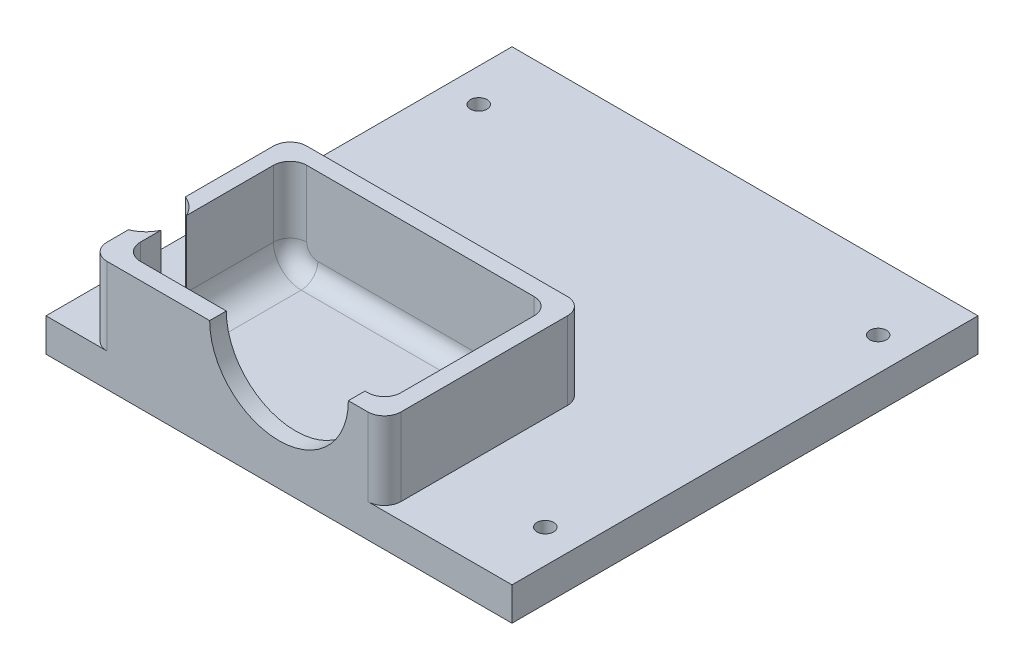
SolidWorks part; units mm, degrees
material "PVB"
ref_plane "Front Plane" through (0, 0, 0) normal (0, 0, 1) x (1, 0, 0)
ref_plane "Top Plane" through (0, 0, 0) normal (0, 1, 0) x (1, 0, 0)
ref_plane "Right Plane" through (0, 0, 0) normal (1, 0, 0) x (0, 0, -1)
sketch "Sketch1" plane through (0, 0, 0) normal (0, 1, 0) x (1, 0, 0)
  line L1 (0, 0) -> (84, 0)
  line L2 (0, 0) -> (0, 84)
  line L3 (0, 84) -> (84, 84)
  line L4 (84, 0) -> (84, 84)
  dimension "D1" = 84
  dimension "D2" = 84
extrude "Boss-Extrude1" add sketch "Sketch1" along normal blind 6
sketch "Sketch2" plane through (0, 6, 0) normal (0, 1, 0) x (1, 0, 0)
  line L0 (84, 84) -> (0, 84) construction
  line L1 (0, 84) -> (0, 0) construction
  line L2 (0, 0) -> (84, 0) construction
  line L3 (84, 0) -> (84, 84) construction
  circle A0 centre (6, 72) radius 1.5
  circle A1 centre (6, 12) radius 1.5
  circle A2 centre (78, 12) radius 1.5
  circle A3 centre (78, 72) radius 1.5
  dimension "D1" = 3
  dimension "D2" = 3
  dimension "D3" = 3
  dimension "D4" = 3
  dimension "D6" = 6
  dimension "D7" = 12
  dimension "D8" = 6
  dimension "D9" = 6
  dimension "D10" = 12
  dimension "D11" = 6
  dimension "D5" = 12
  dimension "D12" = 12
extrude "Cut-Extrude1" cut sketch "Sketch2" against normal through all
ref_plane "Plane1" through (0, 0, -42) normal (0, 0, 1) x (1, 0, 0)
sketch "Sketch4" plane through (0, 6, 0) normal (0, 1, 0) x (1, 0, 0)
  line L0 (3, 21) -> (3, 9)
  line L1 (3, 9) -> (13, 9)
  line L2 (13, 15) -> (8, 21)
  line L3 (3, 21) -> (8, 21)
  line L4 (8, 21) -> (13, 15)
  line L5 (13, 15) -> (13, 9)
  line L6 (0, 84) -> (0, 0) construction
  line L7 (0, 0) -> (84, 0) construction
  circle A0 centre (6, 12) radius 1.5
  circle A1 centre (6, 12) radius 1.5 construction
  dimension "D1" = 3
  dimension "D2" = 9
  dimension "D3" = 12
  dimension "D4" = 10
  dimension "D5" = 6
  dimension "D6" = 5
ref_plane "Plane2" through (42, 0, 0) normal (-1, 0, 0) x (0, 0, 1)
sketch "Sketch5" plane through (0, 6, 0) normal (0, 1, 0) x (1, 0, 0)
  line L0 (8, 36) -> (8, 0)
  line L1 (8, 36) -> (61, 36)
  line L2 (8, 0) -> (61, 0)
  line L3 (61, 36) -> (61, 0)
  line L4 (8, 36) -> (61, 0) construction
  line L5 (8, 0) -> (61, 36) construction
  line L6 (42, 3.3) -> (42, -3.3) construction
  line L12 (0, 0) -> (84, 0) construction
  point P1 (34.5, 18)
  dimension "D1" = 53
  dimension "D2" = 36
  dimension "D3" = 7.5
extrude "Boss-Extrude2" add sketch "Sketch5" along normal blind 22
sketch "Sketch6" plane through (0, 28, 0) normal (0, 1, 0) x (1, 0, 0)
  line L14 (58, 33) -> (11, 33)
  line L15 (11, 33) -> (11, 3)
  line L16 (11, 3) -> (58, 3)
  line L17 (58, 3) -> (58, 33)
  line L18 (58, 33) -> (11, 33)
  line L19 (11, 33) -> (11, 3)
  line L20 (11, 3) -> (58, 3)
  line L21 (58, 3) -> (58, 33)
  dimension "D1" = 3
extrude "Cut-Extrude5" cut sketch "Sketch6" against normal blind 25
fillet "Fillet1" radius 3 10 edges at (58, 15.5, -33) (11, 15.5, -33) (58, 15.5, -3) (11, 15.5, -3) (8, 17, -36) (61, 17, 0) (61, 17, -36) (8, 17, 0) (34.5, 3, -3) (34.5, 3, -33)
fillet "Fillet2" radius 5 6 edges at (11.8787, 3.8787, -3.8787) (11.8787, 3.8787, -32.1213) (57.1213, 3.8787, -32.1213) (57.1213, 3.8787, -3.8787) (58, 3, -18) (11, 3, -18)
sketch "Sketch8" plane through (0, 0, 0) normal (0, 0, 1) x (1, 0, 0)
  line L1 (0, 0) -> (84, 0) construction
  line L3 (61, 28) -> (61, 6) construction
  circle A0 centre (42, 20) radius 12.5
  dimension "D2" = 25
  dimension "D1" = 19
  dimension "D3" = 20
extrude "Cut-Extrude6" cut sketch "Sketch8" against normal blind 10
sketch "Sketch9" plane through (0, 0, 0) normal (0, 0, 1) x (1, 0, 0)
  line L0 (0, 0) -> (84, 0) construction
  line L1 (0, 28) -> (84, 28)
  line L2 (0, 28) -> (0, 20)
  line L3 (0, 20) -> (84, 20)
  line L4 (84, 28) -> (84, 20)
  line L5 (84, 6) -> (84, 0) construction
  line L6 (0, 6) -> (0, 0) construction
  line L7 (11, 28) -> (32.3953, 28) construction
  dimension "D1" = 20
extrude "Cut-Extrude7" cut sketch "Sketch9" against normal through all both and the other way through all
sketch "Sketch11" plane through (0, 0, 0) normal (0, -1, 0) x (1, 0, 0)
  line L0 (3, -9) -> (13, -9)
  line L1 (13, -9) -> (13, -15)
  line L2 (13, -15) -> (8, -21)
  line L3 (8, -21) -> (3, -21)
  line L4 (3, -21) -> (3, -9)
extrude "Cut-Extrude8" cut sketch "Sketch11" against normal blind 3
mirror "Mirror1" about plane through (0, 0, -42) normal (0, 0, 1) of "Cut-Extrude8" second plane through (42, 0, 0) second plane normal (-1, 0, 0)
sketch "Sketch13" plane through (0, 20, 0) normal (0, 1, 0) x (1, 0, 0)
  line L12 (54.5, 0) -> (58, 0)
  line L13 (61, 3) -> (61, 33)
  line L14 (58, 36) -> (11, 36)
  line L15 (8, 33) -> (8, 3)
  line L16 (11, 0) -> (29.5, 0)
  line L17 (29.5, 0) -> (29.5, 3)
  line L18 (29.5, 3) -> (14, 3)
  line L19 (11, 6) -> (11, 30)
  line L20 (14, 33) -> (55, 33)
  line L21 (58, 30) -> (58, 6)
  line L22 (55, 3) -> (54.5, 3)
  line L23 (54.5, 3) -> (54.5, 0)
  line L24 (54.5, 0) -> (58, 0)
  line L25 (61, 3) -> (61, 33)
  line L26 (58, 36) -> (11, 36)
  line L27 (8, 33) -> (8, 3)
  line L28 (11, 0) -> (29.5, 0)
  line L29 (29.5, 0) -> (29.5, 3)
  line L30 (29.5, 3) -> (14, 3)
  line L31 (11, 6) -> (11, 30)
  line L32 (14, 33) -> (55, 33)
  line L33 (58, 30) -> (58, 6)
  line L34 (55, 3) -> (54.5, 3)
  line L35 (54.5, 3) -> (54.5, 0)
  circle A0 centre (6, 12) radius 1.5 construction
  circle A1 centre (6, 12) radius 1.5
  circle A2 centre (6, 12) radius 5.5
  arc A8 (58, 0) -> (61, 3) centre (58, 3) ccw
  arc A9 (61, 33) -> (58, 36) centre (58, 33) ccw
  arc A10 (11, 36) -> (8, 33) centre (11, 33) ccw
  arc A11 (8, 3) -> (11, 0) centre (11, 3) ccw
  arc A12 (11, 6) -> (14, 3) centre (14, 6) ccw
  arc A13 (14, 33) -> (11, 30) centre (14, 30) ccw
  arc A14 (58, 30) -> (55, 33) centre (55, 30) ccw
  arc A15 (55, 3) -> (58, 6) centre (55, 6) ccw
  arc A16 (58, 0) -> (61, 3) centre (58, 3) ccw
  arc A17 (61, 33) -> (58, 36) centre (58, 33) ccw
  arc A18 (11, 36) -> (8, 33) centre (11, 33) ccw
  arc A19 (8, 3) -> (11, 0) centre (11, 3) ccw
  arc A20 (11, 6) -> (14, 3) centre (14, 6) ccw
  arc A21 (14, 33) -> (11, 30) centre (14, 30) ccw
  arc A22 (58, 30) -> (55, 33) centre (55, 30) ccw
  arc A23 (55, 3) -> (58, 6) centre (55, 6) ccw
  dimension "D2" = 11
  dimension "D1" = 0
extrude "Cut-Extrude9" cut sketch "Sketch13" against normal up to surface (14 mm away) contours L27 A2 L31 region at (9.3364, 20, -12) up to face at (6, 6, -70.5)
